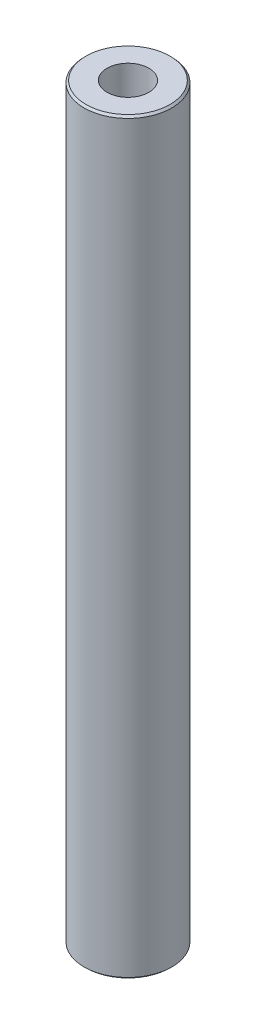
SolidWorks part; units mm, degrees
ref_plane "Front Plane" through (0, 0, 0) normal (0, 0, 1) x (1, 0, 0)
ref_plane "Top Plane" through (0, 0, 0) normal (0, 1, 0) x (1, 0, 0)
ref_plane "Right Plane" through (0, 0, 0) normal (1, 0, 0) x (0, 0, -1)
sketch "Sketch1" plane through (0, 0, 0) normal (0, 1, 0) x (1, 0, 0)
  circle A0 centre (0, 0) radius 32.5
  dimension "SHAFT_OD" = 65
extrude "Boss-Extrude1" add sketch "Sketch1" along normal blind 554.0677
sketch "Sketch2" plane through (0, 0, 0) normal (0, 1, 0) x (1, 0, 0)
  circle A0 centre (0, 0) radius 15.5088
  dimension "BORE_D" = 31.0176
extrude "Cut-Extrude1" cut sketch "Sketch2" along normal through all
chamfer "Chamfer1" distance 1.5125 angle 42.738 2 edges at (0, 554.0677, 32.5) (0, 0, 32.5) first distance on face at (0, 554.0677, 32.5) first distance on face at (0, 0, 15.5088)
